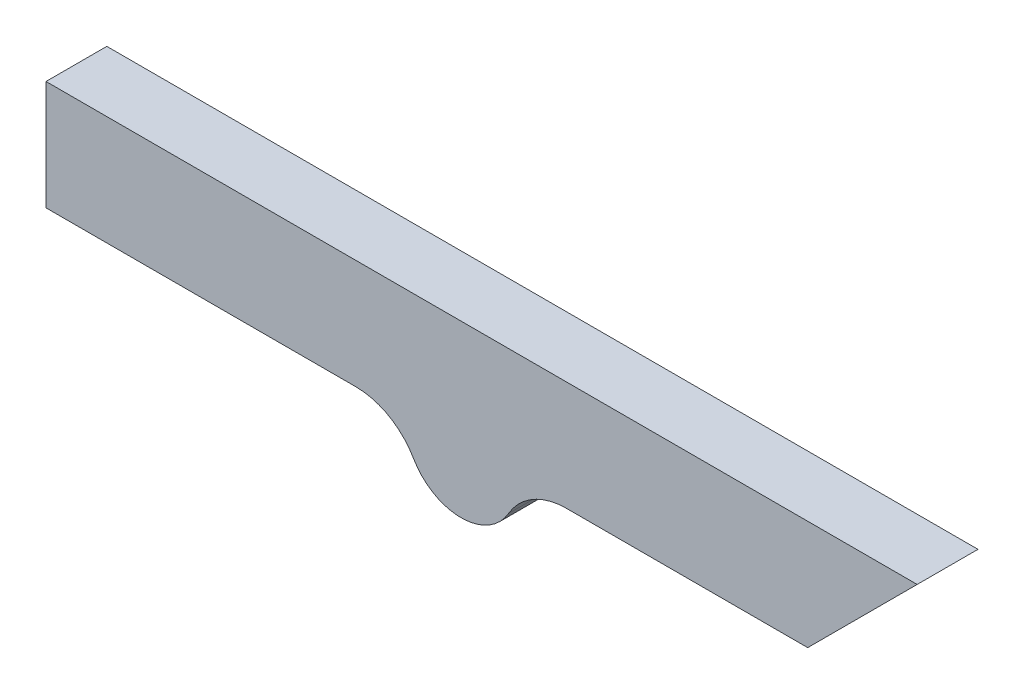
SolidWorks part; units mm, degrees
ref_plane "Front Plane" through (0, 0, 0) normal (0, 0, 1) x (1, 0, 0)
ref_plane "Top Plane" through (0, 0, 0) normal (0, 1, 0) x (1, 0, 0)
ref_plane "Right Plane" through (0, 0, 0) normal (1, 0, 0) x (0, 0, -1)
sketch "Sketch1" plane through (0, 0, 0) normal (0, 0, 1) x (1, 0, 0)
  line L0 (22.9331, 13.175) -> (11.75, 13.175)
  line L1 (11.75, 13.175) -> (11.75, 11.375)
  line L2 (11.75, 11.375) -> (13.8429, 11.375)
  line L3 (17.3071, 11.375) -> (21.1331, 11.375)
  line L4 (21.1331, 11.375) -> (22.9331, 13.175)
  line L5 (21.1745, 11.275) -> (23.1745, 13.275)
  line L6 (23.1745, 13.275) -> (11.65, 13.275)
  line L7 (11.65, 13.275) -> (11.65, 11.275)
  line L8 (11.65, 11.275) -> (13.8429, 11.275)
  line L9 (17.3071, 11.275) -> (21.1745, 11.275)
  line L10 (21.1745, 11.275) -> (23.1745, 13.275)
  line L11 (23.1745, 13.275) -> (11.65, 13.275)
  line L12 (11.65, 13.275) -> (11.65, 11.275)
  line L13 (11.65, 11.275) -> (13.8429, 11.275)
  line L14 (17.3071, 11.275) -> (21.1745, 11.275)
  line L15 (22.9331, 13.175) -> (23.0745, 13.175)
  line L16 (11.75, 13.175) -> (8.75, 13.175)
  line L17 (11.75, 13.175) -> (11.75, 11.375)
  line L18 (11.75, 11.375) -> (8.75, 11.375)
  line L19 (21.1331, 11.375) -> (21.2745, 11.375)
  line L29 (8.75, 13.175) -> (8.75, 11.375)
  arc A0 (14.7956, 10.825) -> (13.8429, 11.375) centre (13.8429, 10.275) ccw
  arc A1 (14.7956, 10.825) -> (16.3544, 10.825) centre (15.575, 11.275) ccw
  arc A2 (17.3071, 11.375) -> (16.3544, 10.825) centre (17.3071, 10.275) ccw
  arc A7 (14.709, 10.775) -> (13.8429, 11.275) centre (13.8429, 10.275) ccw
  arc A8 (14.709, 10.775) -> (16.441, 10.775) centre (15.575, 11.275) ccw
  arc A9 (17.3071, 11.275) -> (16.441, 10.775) centre (17.3071, 10.275) ccw
  arc A10 (14.709, 10.775) -> (13.8429, 11.275) centre (13.8429, 10.275) ccw
  arc A11 (14.709, 10.775) -> (16.441, 10.775) centre (15.575, 11.275) ccw
  arc A12 (17.3071, 11.275) -> (16.441, 10.775) centre (17.3071, 10.275) ccw
  dimension "D3" = 3
  dimension "D1" = 0
  dimension "D2" = 0.1
extrude "Shape" add sketch "Sketch1" along normal blind 1 contours A2 L3 L4 L0 L1 L2 A0 A1 | L4 L19 L10 L15 | L18 L1 L16 L12 | L16 L29 L18 L12 region at (16.7953, 12.1929, 0) region at (22.1038, 12.275, 0) region at (11.7, 12.275, 0) region at (10.2, 12.275, 0)
sketch "Facing" plane through (0, 0, 1) normal (0, 0, 1) x (1, 0, 0)
  line L0 (8.75, 12.275) -> (23.0745, 12.275)
  line L2 (23.0745, 13.175) -> (23.0745, 11.375) construction
  line L3 (8.75, 13.175) -> (8.75, 11.375) construction
